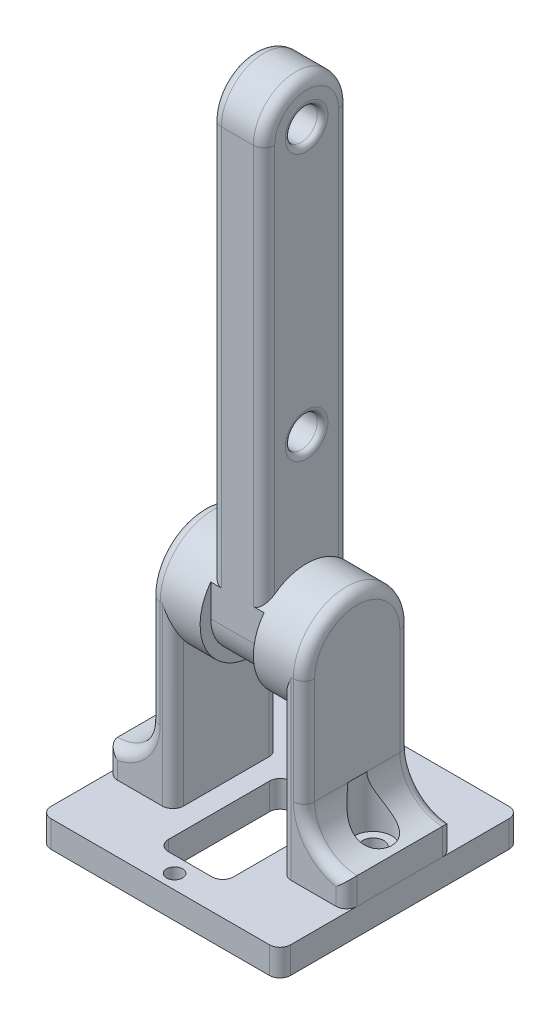
SolidWorks part; units mm, degrees
other "Base"
other "Brazo"
ref_plane "Alzado" through (0, 0, 0) normal (0, 0, 1) x (1, 0, 0)
ref_plane "Planta" through (0, 0, 0) normal (0, 1, 0) x (1, 0, 0)
ref_plane "Vista lateral" through (0, 0, 0) normal (1, 0, 0) x (0, 0, -1)
sketch "Croquis1" plane through (0, 0, 0) normal (0, 1, 0) x (1, 0, 0)
  line L0 (-17.5, 5.35) -> (17.5, 5.35) construction
  line L1 (-6.1, -11.5) -> (6.1, -11.5)
  line L2 (-6.1, -11.5) -> (-6.1, 11.5)
  line L3 (-6.1, 11.5) -> (6.1, 11.5)
  line L4 (6.1, -11.5) -> (6.1, 11.5)
  line L5 (-6.1, -11.5) -> (6.1, 11.5) construction
  line L6 (-6.1, 11.5) -> (6.1, -11.5) construction
  line L11 (0, 14.45) -> (0, -14.45) construction
  line L13 (-17.5, 7.35) -> (-6.1, 7.35) construction
  line L18 (-6.1, 11.5) -> (6.1, 11.5) construction
  line L22 (-22.5, -17.15) -> (22.5, -17.15)
  line L23 (-22.5, -17.15) -> (-22.5, 27.85)
  line L24 (-22.5, 27.85) -> (22.5, 27.85)
  line L25 (22.5, -17.15) -> (22.5, 27.85)
  line L26 (-22.5, -17.15) -> (22.5, 27.85) construction
  line L27 (-22.5, 27.85) -> (22.5, -17.15) construction
  line L30 (-6.1, -11.5) -> (6.1, -11.5) construction
  circle A0 centre (-17.5, 5.35) radius 2
  circle A1 centre (17.5, 5.35) radius 2
  circle A12 centre (0, 14.45) radius 1.5
  circle A13 centre (0, -14.45) radius 1.5
  point P0 (0, 0)
  point P14 (0, 5.35)
  point P17 (0, 0)
  point P41 (0, 5.35)
  dimension "D4" = 4
  dimension "D5" = 45
  dimension "D6" = 45
  dimension "D7" = 4
  dimension "D12" = 3
  dimension "D13" = 3
  dimension "D1" = 12.2
  dimension "D2" = 23
  dimension "D3" = 9.1
  dimension "D8" = 35
  dimension "D9" = 28.9
extrude "Saliente-Extruir1" add sketch "Croquis1" against normal blind 5 contours L25 L24 L23 A1 A0 L4 L1 L2 L3 region at (-21.8636, 0, -5.35)
sketch "Croquis2" plane through (0, -5, 0) normal (0, -1, 0) x (1, 0, 0)
  line L4 (-22.5, -27.85) -> (22.5, -27.85)
  line L5 (22.5, 17.15) -> (-22.5, 17.15)
  line L6 (22.5, 17.15) -> (-22.5, 17.15)
  line L7 (-22.5, 17.15) -> (-22.5, -27.85)
  line L8 (-22.5, -27.85) -> (22.5, -27.85)
  line L12 (-22.5, 17.15) -> (-22.5, -27.85)
  line L13 (22.5, -27.85) -> (22.5, 17.15)
  line L14 (22.5, -27.85) -> (22.5, 17.15)
  circle A0 centre (0, -14.45) radius 1.5 construction
  circle A1 centre (0, -14.45) radius 1.5
  circle A2 centre (0, 14.45) radius 1.5 construction
  circle A3 centre (0, 14.45) radius 1.5
  circle A12 centre (0, 14.45) radius 2
  circle A13 centre (0, -14.45) radius 2
  circle M17 centre (0, 14.45) radius 1.5
  circle M18 centre (0, -14.45) radius 1.5
  dimension "D2" = 0.5
  dimension "D3" = 0.5
  dimension "D1" = 0
extrude "Cortar-Extruir1" cut sketch "Croquis2" against normal blind 2 contours A13 M18 | A12 M17 region at (-1.9434, -5, 14.45) region at (-1.9434, -5, -14.45)
sketch "Croquis3" plane through (0, 0, 0) normal (1, 0, 0) x (0, 0, -1)
  line L1 (-17.15, 0) -> (27.85, 0) construction
  line L3 (5.35, 0) -> (5.35, 122) construction
  line L4 (-2.65, 114) -> (-2.65, 33)
  line L6 (13.35, 114) -> (13.35, 33)
  circle A1 centre (5.35, 33) radius 8
  circle A3 centre (5.35, 64) radius 3
  circle A4 centre (5.35, 114) radius 3
  circle A5 centre (5.35, 114) radius 8
  point P2 (5.35, 61)
  point P3 (5.35, 41)
  point P6 (5.35, 25)
  point P20 (5.35, 117)
  dimension "D1" = 50
  dimension "D3" = 25
  dimension "D5" = 6
  dimension "D6" = 6
  dimension "D7" = 5
  dimension "D2" = 20
extrude "Saliente-Extruir2" add sketch "Croquis3" along normal mid plane 10 separate body contours A1 L3 A3 A5 L4 | L3 A1 L6 A5 A3 | L3 A5 A4 | A5 L3 A4 | A1 region at (0, 73.7518, -1.1637) region at (0, 73.7518, -9.5363) region at (0, 114, -1.6074) region at (0, 114, -9.0926)
sketch "Croquis4" plane through (0, 0, 0) normal (0, 1, 0) x (1, 0, 0)
  line L5 (22.5, -17.15) -> (22.5, 27.85) construction
  line L6 (12.5, -4.65) -> (22.5, -4.65)
  line L7 (12.5, -4.65) -> (12.5, 15.35)
  line L8 (12.5, 15.35) -> (22.5, 15.35)
  line L9 (22.5, -4.65) -> (22.5, 15.35)
  line L10 (12.5, -4.65) -> (22.5, 15.35) construction
  line L11 (12.5, 15.35) -> (22.5, -4.65) construction
  line L12 (12.5, 15.35) -> (10.1, 15.35)
  line L13 (10.1, 15.35) -> (10.1, -4.65)
  line L14 (10.1, -4.65) -> (12.5, -4.65)
  line L15 (6.1, -11.5) -> (6.1, 11.5) construction
  line L16 (14.5, 15.35) -> (14.5, -4.65) construction
  circle A0 centre (17.5, 5.35) radius 2 construction
  circle A1 centre (17.5, 5.35) radius 2
  circle A2 centre (17.5, 5.35) radius 3.5
  point P15 (15.5, 5.35)
  circle M12 centre (17.5, 5.35) radius 2
  dimension "D6" = 1.5
  dimension "D1" = 10
  dimension "D2" = 20
  dimension "D3" = 4
  dimension "D4" = 1
  dimension "D5" = 4.4
ref_plane "Plano1" through (0, 0, 4.65) normal (0, 0, 1) x (1, 0, 0)
sketch "Croquis5" plane through (0, 0, 4.65) normal (0, 0, 1) x (1, 0, 0)
  line L0 (10.1, 0) -> (10.1, 33)
  line L1 (5, 33) -> (-5, 33) construction
  line L2 (14.5, 0) -> (14.5, 13) construction
  line L4 (14.5, 13) -> (14.5, 33)
  line L5 (14.5, 33) -> (10.1, 33)
  line L6 (10.1, 0) -> (22.5, 0)
  line L7 (22.5, 0) -> (22.5, 5)
  arc A1 (22.5, 5) -> (14.5, 13) centre (22.5, 13) cw
  point P1 (22.5, 0)
  dimension "D1" = 5
extrude "Saliente-Extruir4" add sketch "Croquis5" against normal up to vertex (20 mm away) separate body contours L6 L2 L4 L5 L0 | L2 L6 region at (12.3, 16.5, 4.65) region at (17.9343, 3.5957, 4.65) up to point (22.5, 0, -15.35)
extrude "Cortar-Extruir2" cut sketch "Croquis4" along normal blind 10 contours A1
sketch "Croquis6" plane through (14.5, 0, 0) normal (1, 0, 0) x (0, 0, -1)
  circle A0 centre (5.35, 33) radius 10
extrude "Saliente-Extruir5" add sketch "Croquis6" against normal up to surface (9.5 mm away) up to face at (5, 73.5, -5.35)
fillet "Redondeo3" radius 2 8 edges at (-22.5, -2.5, -27.85) (6.1, -2.5, 11.5) (6.1, -2.5, -11.5) (-6.1, -2.5, 11.5) (-6.1, -2.5, -11.5) (-22.5, -2.5, 17.15) (22.5, -2.5, 17.15) (22.5, -2.5, -27.85)
fillet "Redondeo4" radius 1 4 edges at (-5, 64, -8.35) (5, 64, -8.35) (-5, 114, -8.35) (5, 114, -8.35)
mirror "Simetría3" about plane through (0, 0, 0) normal (1, 0, 0) of bodies 119
combine bodies "Combinar2" operation type add bodies to combine 115 122 119
fillet "Redondeo5" radius 2 24 edges at (-5, 76.5, 2.65) (-5, 122, -5.35) (5, 76.5, 2.65) (5, 122, -5.35) (14.5, 23, -15.35) (14.5, 43, -5.35) (-14.5, 23, -15.35) (-14.5, 43, -5.35) (-5, 76.5, -13.35) (5, 76.5, -13.35) (-10.1, 16.5, -15.35) (10.1, 16.5, -15.35) (14.5, 23, 4.65) (10.1, 16.5, 4.65) (-10.1, 16.5, 4.65) (-14.5, 23, 4.65) (16.8431, 7.3431, 4.65) (16.8431, 7.3431, -15.35) (-16.8431, 7.3431, 4.65) (-16.8431, 7.3431, -15.35) (22.5, 2.5, -15.35) (22.5, 2.5, 4.65) (-22.5, 2.5, -15.35) (-22.5, 2.5, 4.65)
extrude "Cortar-Extruir3" cut sketch "Croquis4<3>" against normal up to vertex (-3.202 mm away) from vertex contours A2 M12 region at (14.099, 0, -5.35) up to point (20.5, 3.202, 4.65) starting at point (14.5, 13, 2.65)
sketch "Croquis4<3>" plane through (0, 0, 0) normal (0, 1, 0) x (1, 0, 0) same geometry as "Croquis4"
sketch "Croquis7" plane through (0, 0, 0) normal (0, 1, 0) x (1, 0, 0)
  circle A0 centre (-17.5, 5.35) radius 2 construction
  circle A1 centre (-17.5, 5.35) radius 2
  circle A2 centre (-17.5, 5.35) radius 3.5
  dimension "D1" = 1.5
extrude "Cortar-Extruir4" cut sketch "Croquis7" against normal up to vertex (-3.202 mm away) from vertex up to point (-20.5, 3.202, 4.65) starting at point (-14.5, 13, 2.65)
